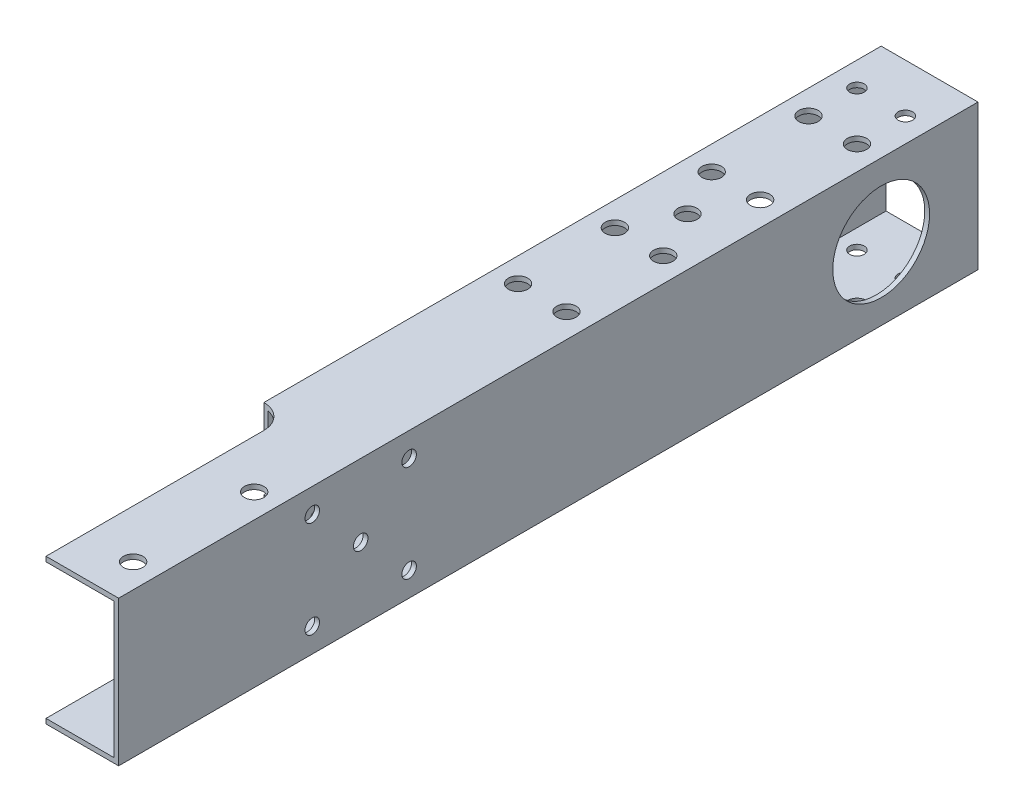
SolidWorks part; units mm, degrees
material "6061-T4 (SS)"
ref_plane "前视基准面" through (0, 0, 0) normal (0, 0, 1) x (1, 0, 0)
ref_plane "上视基准面" through (0, 0, 0) normal (0, 1, 0) x (1, 0, 0)
ref_plane "右视基准面" through (0, 0, 0) normal (1, 0, 0) x (0, 0, -1)
other "Configuration Table"
sketch "草图1" plane through (0, 0, 0) normal (0, 0, 1) x (1, 0, 0)
  line L1 (-10, -15) -> (10, -15)
  line L2 (-10, -15) -> (-10, 15)
  line L3 (-10, 15) -> (10, 15)
  line L4 (10, -15) -> (10, 15)
  line L5 (-10, -15) -> (10, 15) construction
  line L6 (-10, 15) -> (10, -15) construction
  point P0 (0, 0)
  dimension "D1" = 20
  dimension "D2" = 30
extrude "拉伸-薄壁1" add sketch "草图1" along normal blind 177.5 thin thin type one direction reverse wall 1
sketch "草图2" plane through (0, 15, 0) normal (0, 1, 0) x (1, 0, 0)
  line L0 (-5, -10) -> (5, -10) construction
  line L1 (0, 0) -> (0, -10) construction
  circle A0 centre (5, -10) radius 1.5
  circle A1 centre (-5, -10) radius 1.5
  dimension "D3" = 3
  dimension "D1" = 10
  dimension "D2" = 10
extrude "切除-拉伸1" cut sketch "草图2" against normal up to surface (30 mm away) up to face at (0, -15, 88.75)
sketch "草图3" plane through (0, 15, 0) normal (0, 1, 0) x (1, 0, 0)
  line L1 (-10, -177.5) -> (-5, -177.5)
  line L2 (-10, -177.5) -> (-10, -127.5)
  line L3 (-10, -127.5) -> (-5, -127.5)
  line L4 (-5, -177.5) -> (-5, -127.5)
  dimension "D1" = 5
  dimension "D2" = 50
extrude "切除-拉伸2" cut sketch "草图3" against normal up to surface (30 mm away) up to face at (5, -15, 11.5)
fillet "圆角1" radius 5 1 edges at (-5, 14.5, 127.5)
sketch "草图4" plane through (0, 15, 0) normal (0, 1, 0) x (1, 0, 0)
  line L0 (0, -177.5) -> (0, -157) construction
  line L1 (10, -177.5) -> (-5, -177.5) construction
  line L2 (10, -177.5) -> (10, 0) construction
  line L4 (-5, -169.5) -> (5, -169.5) construction
  line L5 (-5, -169.5) -> (-5, -144.5) construction
  line L6 (-5, -144.5) -> (5, -144.5) construction
  line L7 (5, -169.5) -> (5, -144.5) construction
  line L8 (-5, -169.5) -> (5, -144.5) construction
  line L9 (-5, -144.5) -> (5, -169.5) construction
  circle A0 centre (5, -144.5) radius 2
  circle A1 centre (5, -169.5) radius 2
  dimension "D5" = 4
  dimension "D1" = 10
  dimension "D2" = 8
  dimension "D3" = 25
  dimension "D4" = 10
extrude "切除-拉伸3" cut sketch "草图4" against normal up to surface (30 mm away) up to face at (5, -15, 11.5)
sketch "草图5" plane through (0, -15, 0) normal (0, -1, 0) x (1, 0, 0)
  line L0 (0, 0) -> (0, 50) construction
  line L2 (-5, 40) -> (5, 40) construction
  line L3 (-5, 40) -> (-5, 60) construction
  line L4 (-5, 60) -> (5, 60) construction
  line L5 (5, 40) -> (5, 60) construction
  line L6 (-5, 40) -> (5, 60) construction
  line L7 (-5, 60) -> (5, 40) construction
  line L8 (-5, 20) -> (5, 20) construction
  line L9 (-5, 20) -> (-5, 80) construction
  line L10 (-5, 80) -> (5, 80) construction
  line L11 (5, 20) -> (5, 80) construction
  line L12 (-5, 20) -> (5, 80) construction
  line L13 (-5, 80) -> (5, 20) construction
  circle A0 centre (5, 20) radius 2
  circle A1 centre (5, 40) radius 2
  circle A2 centre (5, 60) radius 2
  circle A3 centre (5, 80) radius 2
  circle A4 centre (-5, 80) radius 2
  circle A5 centre (-5, 60) radius 2
  circle A6 centre (-5, 40) radius 2
  circle A7 centre (-5, 20) radius 2
  circle A8 centre (5, 10) radius 1.5 construction
  circle A9 centre (0, 50) radius 2
  dimension "D3" = 10
  dimension "D5" = 4
  dimension "D1" = 20
  dimension "D2" = 20
  dimension "D4" = 10
extrude "切除-拉伸4" cut sketch "草图5" against normal up to surface (30 mm away) up to face at (5, 15, 146.5)
sketch "草图6" plane through (10, 0, 0) normal (1, 0, 0) x (0, 0, -1)
  line L0 (-177.5, -15) -> (-177.5, 15) construction
  line L1 (-137.5, -10) -> (-117.5, -10) construction
  line L2 (-137.5, -10) -> (-137.5, 10) construction
  line L3 (-137.5, 10) -> (-117.5, 10) construction
  line L4 (-117.5, -10) -> (-117.5, 10) construction
  line L5 (-137.5, -10) -> (-117.5, 10) construction
  line L6 (-137.5, 10) -> (-117.5, -10) construction
  line L7 (-127.5, 0) -> (-177.5, 0) construction
  line L9 (0, 0) -> (-20, 0) construction
  line L10 (0, -15) -> (0, 15) construction
  circle A0 centre (-127.5, 0) radius 1.5
  circle A1 centre (-117.5, 10) radius 1.5
  circle A2 centre (-117.5, -10) radius 1.5
  circle A3 centre (-137.5, -10) radius 1.5
  circle A4 centre (-137.5, 10) radius 1.5
  circle A5 centre (-20, 0) radius 10
  point P0 (-127.5, 0)
  dimension "D3" = 3
  dimension "D4" = 20
  dimension "D1" = 50
  dimension "D2" = 20
  dimension "D5" = 20
extrude "切除-拉伸5" cut sketch "草图6" against normal up to surface (20 mm away) up to face at (-10, 0, 63.75)
